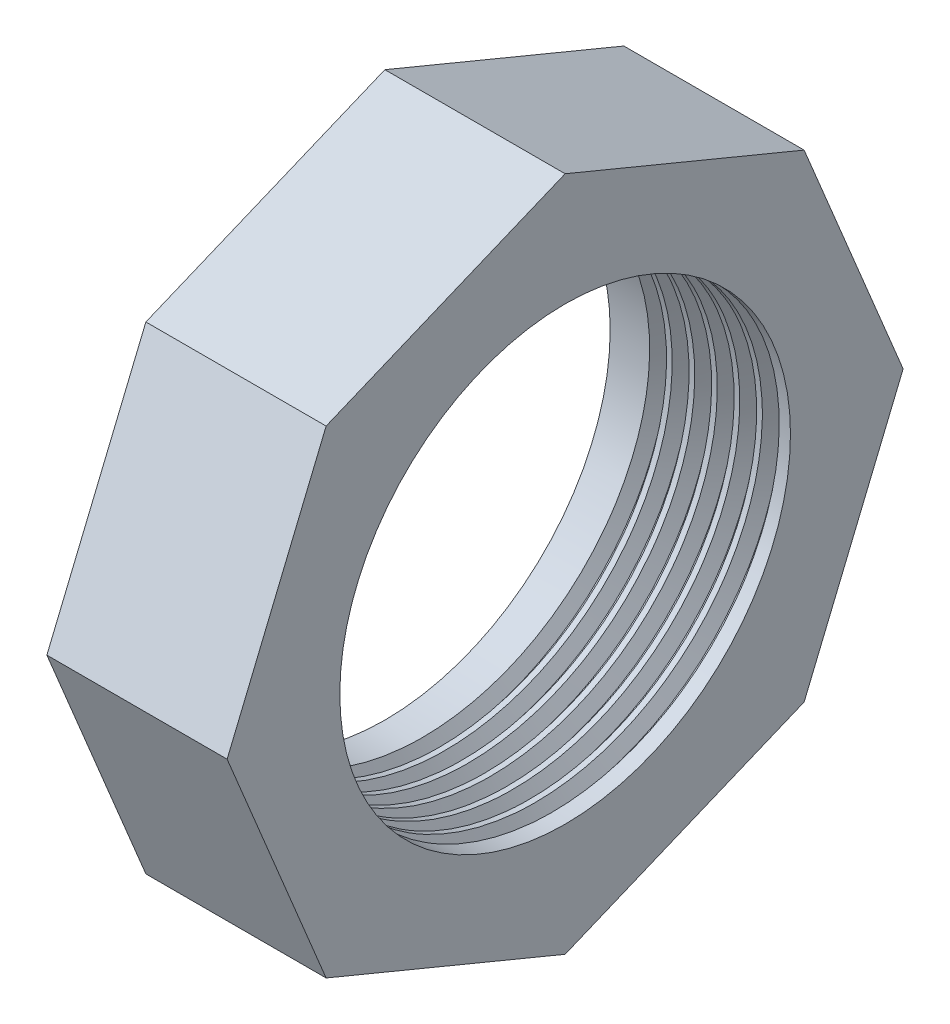
SolidWorks part; units mm, degrees
ref_plane "Front Plane" through (0, 0, 0) normal (0, 0, 1) x (1, 0, 0)
ref_plane "Top Plane" through (0, 0, 0) normal (0, 1, 0) x (1, 0, 0)
ref_plane "Right Plane" through (0, 0, 0) normal (1, 0, 0) x (0, 0, -1)
sketch "Sketch1" plane through (0, 0, 0) normal (1, 0, 0) x (0, 0, -1)
  line L0 (-3.75, 0) -> (3.75, 0) construction
  line L1 (-2.6517, -2.6517) -> (2.6517, 2.6517) construction
  line L2 (-2.6517, 2.6517) -> (2.6517, -2.6517) construction
  line L3 (0, 3.75) -> (0, -3.75) construction
  line L4 (-2.6517, 2.6517) -> (0, 3.75)
  line L5 (0, 3.75) -> (2.6517, 2.6517)
  line L6 (-2.6517, -2.6517) -> (0, -3.75)
  line L7 (0, -3.75) -> (2.6517, -2.6517)
  line L8 (-3.75, 0) -> (-2.6517, 2.6517)
  line L10 (-2.6517, -2.6517) -> (-3.75, 0)
  line L11 (2.6517, -2.6517) -> (3.75, 0)
  line L12 (3.75, 0) -> (2.6517, 2.6517)
  circle A0 centre (0, 0) radius 2.5
  point P11 (0, 0)
  point P12 (0, 0)
  point P13 (0, 0)
  point P14 (0, 0)
  dimension "D1" = 5
  dimension "D2" = 7.5
  dimension "D3" = 7.5
  dimension "D4" = 7.5
  dimension "D5" = 7.5
  dimension "D6" = 45
  dimension "D7" = 45
extrude "Boss-Extrude1" add sketch "Sketch1" along normal blind 2
thread "Thread1" pitch 0.25 method cut profile "Thread Profile1" start angle 0, offset 0, length 1.5, pitch 0.25, diameter 5
ref_plane "Plane1" through (2, 0, 2.5) normal (0, -1, 0) x (0, 0, 1)
sketch "Thread Profile1" plane through (2, 0, 2.5) normal (0, -1, 0) x (0, 0, 1)
  line L0 (0, 0) -> (0, 0.25) construction
  line L1 (0, 0) -> (0.1353, 0.0781)
  line L2 (0.1353, 0.0781) -> (0.1353, 0.1094)
  line L3 (0.1353, 0.1094) -> (0, 0.1875)
  line L4 (0.1353, 0.0937) -> (0, 0.0937) construction
  line L11 (0, 0) -> (0, 0.1875)
  point P2 (0, 0)
  dimension "Pitch" = 0.25
  dimension "Profile_Angle" = 60
  dimension "Profile_Land" = 0.0312
  dimension "Profile_Height" = 0.1353
